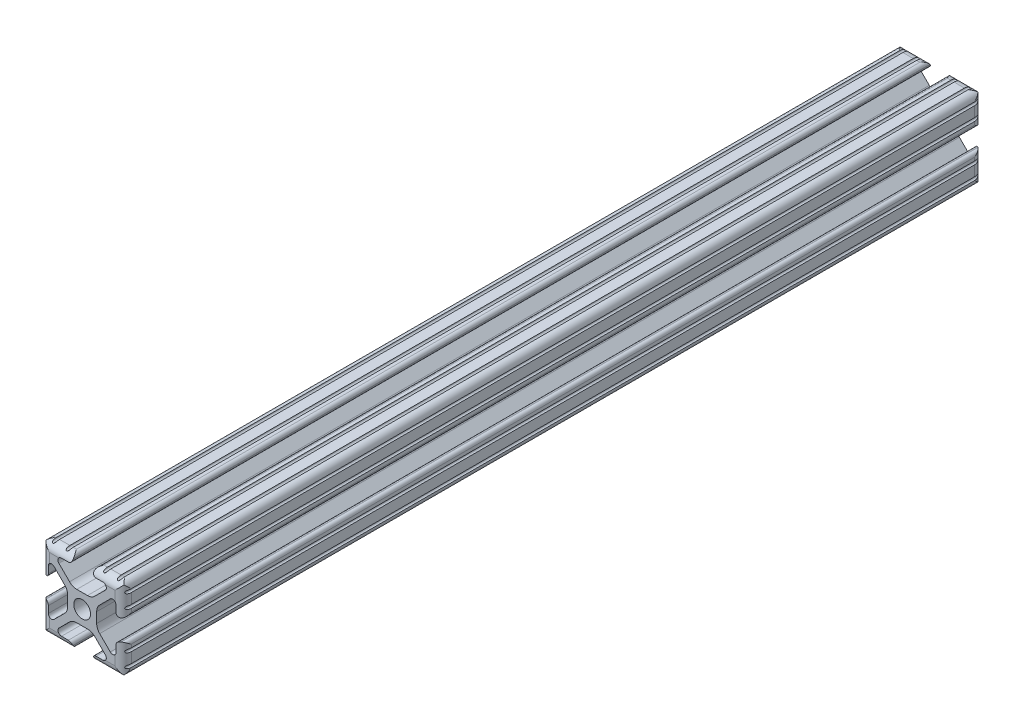
SolidWorks part; units mm, degrees
material "6061 Alloy"
ref_plane "Front Plane" through (0, 0, 0) normal (0, 0, 1) x (1, 0, 0)
ref_plane "Top Plane" through (0, 0, 0) normal (0, 1, 0) x (1, 0, 0)
ref_plane "Right Plane" through (0, 0, 0) normal (1, 0, 0) x (0, 0, -1)
sketch "Sketch1" plane through (0, 0, 0) normal (0, 0, 1) x (1, 0, 0)
  line L88 (-7.1797, -8.6452) -> (-3.9523, -5.4237)
  line L89 (-1.7093, -4.4958) -> (1.7093, -4.4958)
  line L90 (3.9523, -5.4237) -> (7.1797, -8.6452)
  line L91 (6.4164, -10.4902) -> (4.2875, -10.4902)
  line L92 (3.2385, -11.5392) -> (3.2385, -11.651)
  line L93 (4.2875, -12.7) -> (5.3171, -12.7)
  line L94 (6.3331, -12.7) -> (9.5504, -12.7)
  line L95 (12.7, -9.5504) -> (12.7, -6.3331)
  line L96 (12.7, -5.3171) -> (12.7, -4.2875)
  line L97 (11.651, -3.2385) -> (11.5392, -3.2385)
  line L98 (10.4902, -4.2875) -> (10.4902, -6.4021)
  line L99 (8.7371, -7.1294) -> (5.441, -3.8408)
  line L100 (4.5085, -1.5932) -> (4.5085, 1.5932)
  line L101 (5.441, 3.8408) -> (8.7371, 7.1294)
  line L102 (10.4902, 6.4021) -> (10.4902, 4.2875)
  line L103 (11.5392, 3.2385) -> (11.651, 3.2385)
  line L104 (12.7, 4.2875) -> (12.7, 5.3171)
  line L105 (12.7, 6.3331) -> (12.7, 9.5504)
  line L106 (9.5504, 12.7) -> (6.3331, 12.7)
  line L107 (5.3171, 12.7) -> (4.2875, 12.7)
  line L108 (3.2385, 11.651) -> (3.2385, 11.5392)
  line L109 (4.2875, 10.4902) -> (6.4768, 10.4902)
  line L110 (7.207, 8.7244) -> (3.8983, 5.4232)
  line L111 (1.6558, 4.4958) -> (-1.6558, 4.4958)
  line L112 (-3.8983, 5.4232) -> (-7.207, 8.7244)
  line L113 (-6.4768, 10.4902) -> (-4.2875, 10.4902)
  line L114 (-3.2385, 11.5392) -> (-3.2385, 11.651)
  line L115 (-4.2875, 12.7) -> (-5.3171, 12.7)
  line L116 (-6.3331, 12.7) -> (-9.5504, 12.7)
  line L117 (-12.7, 9.5504) -> (-12.7, 6.3331)
  line L118 (-12.7, 5.3171) -> (-12.7, 4.2875)
  line L119 (-11.651, 3.2385) -> (-11.5392, 3.2385)
  line L120 (-10.4902, 4.2875) -> (-10.4902, 6.4021)
  line L121 (-8.7371, 7.1294) -> (-5.441, 3.8408)
  line L122 (-4.5085, 1.5932) -> (-4.5085, -1.5932)
  line L123 (-5.441, -3.8408) -> (-8.7371, -7.1294)
  line L124 (-10.4902, -6.4021) -> (-10.4902, -4.2875)
  line L125 (-11.5392, -3.2385) -> (-11.651, -3.2385)
  line L126 (-12.7, -4.2875) -> (-12.7, -5.3171)
  line L127 (-12.7, -6.3331) -> (-12.7, -9.5504)
  line L128 (-9.5504, -12.7) -> (-6.3331, -12.7)
  line L129 (-5.3171, -12.7) -> (-4.2875, -12.7)
  line L130 (-3.2385, -11.651) -> (-3.2385, -11.5392)
  line L131 (-4.2875, -10.4902) -> (-6.4164, -10.4902)
  circle A1 centre (0, 0) radius 2.6035
  arc A104 (-7.1797, -8.6452) -> (-6.4164, -10.4902) centre (-6.4164, -9.4098) ccw
  arc A105 (-1.7093, -4.4958) -> (-3.9523, -5.4237) centre (-1.7093, -7.6708) ccw
  arc A106 (3.9523, -5.4237) -> (1.7093, -4.4958) centre (1.7093, -7.6708) ccw
  arc A107 (6.4164, -10.4902) -> (7.1797, -8.6452) centre (6.4164, -9.4098) ccw
  arc A108 (4.2875, -10.4902) -> (3.2385, -11.5392) centre (4.2875, -11.5392) ccw
  arc A109 (3.2385, -11.651) -> (4.2875, -12.7) centre (4.2875, -11.651) ccw
  arc A110 (6.3331, -12.7) -> (5.3171, -12.7) centre (5.8251, -12.7) ccw
  arc A111 (10.5664, -12.6998) -> (9.5504, -12.7) centre (10.0584, -12.7) ccw
  arc A112 (10.5664, -12.6998) -> (12.6998, -10.5664) centre (10.5918, -10.5918) ccw
  arc A113 (12.7, -9.5504) -> (12.6998, -10.5664) centre (12.7, -10.0584) ccw
  arc A114 (12.7, -5.3171) -> (12.7, -6.3331) centre (12.7, -5.8251) ccw
  arc A115 (12.7, -4.2875) -> (11.651, -3.2385) centre (11.651, -4.2875) ccw
  arc A116 (11.5392, -3.2385) -> (10.4902, -4.2875) centre (11.5392, -4.2875) ccw
  arc A117 (8.7371, -7.1294) -> (10.4902, -6.4021) centre (9.4628, -6.4021) ccw
  arc A118 (4.5085, -1.5932) -> (5.441, -3.8408) centre (7.6835, -1.5932) ccw
  arc A119 (5.441, 3.8408) -> (4.5085, 1.5932) centre (7.6835, 1.5932) ccw
  arc A120 (10.4902, 6.4021) -> (8.7371, 7.1294) centre (9.4628, 6.4021) ccw
  arc A121 (10.4902, 4.2875) -> (11.5392, 3.2385) centre (11.5392, 4.2875) ccw
  arc A122 (11.651, 3.2385) -> (12.7, 4.2875) centre (11.651, 4.2875) ccw
  arc A123 (12.7, 6.3331) -> (12.7, 5.3171) centre (12.7, 5.8251) ccw
  arc A124 (12.6998, 10.5664) -> (12.7, 9.5504) centre (12.7, 10.0584) ccw
  arc A125 (12.6998, 10.5664) -> (10.5664, 12.6998) centre (10.5918, 10.5918) ccw
  arc A126 (9.5504, 12.7) -> (10.5664, 12.6998) centre (10.0584, 12.7) ccw
  arc A127 (5.3171, 12.7) -> (6.3331, 12.7) centre (5.8251, 12.7) ccw
  arc A128 (4.2875, 12.7) -> (3.2385, 11.651) centre (4.2875, 11.651) ccw
  arc A129 (3.2385, 11.5392) -> (4.2875, 10.4902) centre (4.2875, 11.5392) ccw
  arc A130 (7.207, 8.7244) -> (6.4768, 10.4902) centre (6.4768, 9.4563) ccw
  arc A131 (1.6558, 4.4958) -> (3.8983, 5.4232) centre (1.6558, 7.6708) ccw
  arc A132 (-3.8983, 5.4232) -> (-1.6558, 4.4958) centre (-1.6558, 7.6708) ccw
  arc A133 (-6.4768, 10.4902) -> (-7.207, 8.7244) centre (-6.4768, 9.4563) ccw
  arc A134 (-4.2875, 10.4902) -> (-3.2385, 11.5392) centre (-4.2875, 11.5392) ccw
  arc A135 (-3.2385, 11.651) -> (-4.2875, 12.7) centre (-4.2875, 11.651) ccw
  arc A136 (-6.3331, 12.7) -> (-5.3171, 12.7) centre (-5.8251, 12.7) ccw
  arc A137 (-10.5664, 12.6998) -> (-9.5504, 12.7) centre (-10.0584, 12.7) ccw
  arc A138 (-10.5664, 12.6998) -> (-12.6998, 10.5664) centre (-10.5918, 10.5918) ccw
  arc A139 (-12.7, 9.5504) -> (-12.6998, 10.5664) centre (-12.7, 10.0584) ccw
  arc A140 (-12.7, 5.3171) -> (-12.7, 6.3331) centre (-12.7, 5.8251) ccw
  arc A141 (-12.7, 4.2875) -> (-11.651, 3.2385) centre (-11.651, 4.2875) ccw
  arc A142 (-11.5392, 3.2385) -> (-10.4902, 4.2875) centre (-11.5392, 4.2875) ccw
  arc A143 (-8.7371, 7.1294) -> (-10.4902, 6.4021) centre (-9.4628, 6.4021) ccw
  arc A144 (-4.5085, 1.5932) -> (-5.441, 3.8408) centre (-7.6835, 1.5932) ccw
  arc A145 (-5.441, -3.8408) -> (-4.5085, -1.5932) centre (-7.6835, -1.5932) ccw
  arc A146 (-10.4902, -6.4021) -> (-8.7371, -7.1294) centre (-9.4628, -6.4021) ccw
  arc A147 (-10.4902, -4.2875) -> (-11.5392, -3.2385) centre (-11.5392, -4.2875) ccw
  arc A148 (-11.651, -3.2385) -> (-12.7, -4.2875) centre (-11.651, -4.2875) ccw
  arc A149 (-12.7, -6.3331) -> (-12.7, -5.3171) centre (-12.7, -5.8251) ccw
  arc A150 (-12.6998, -10.5664) -> (-12.7, -9.5504) centre (-12.7, -10.0584) ccw
  arc A151 (-12.6998, -10.5664) -> (-10.5664, -12.6998) centre (-10.5918, -10.5918) ccw
  arc A152 (-9.5504, -12.7) -> (-10.5664, -12.6998) centre (-10.0584, -12.7) ccw
  arc A153 (-5.3171, -12.7) -> (-6.3331, -12.7) centre (-5.8251, -12.7) ccw
  arc A154 (-4.2875, -12.7) -> (-3.2385, -11.651) centre (-4.2875, -11.651) ccw
  arc A155 (-3.2385, -11.5392) -> (-4.2875, -10.4902) centre (-4.2875, -11.5392) ccw
extrude "Boss-Extrude1" add sketch "Sketch1" along normal mid plane 266.7
sketch "Sketch3" plane through (-12.7, 0, 0) normal (-1, 0, 0) x (0, 0, 1)
  line L0 (-133.35, 0) -> (133.35, 0) construction
  line L1 (133.35, -12.6998) -> (-133.35, -12.6998) construction
  line L2 (133.35, -12.6998) -> (133.35, 12.6998) construction
  line L3 (133.35, 12.6998) -> (-133.35, 12.6998) construction
  line L4 (-133.35, -12.6998) -> (-133.35, 12.6998) construction
  circle A0 centre (101.6, 0) radius 3.175
  circle A1 centre (82.55, 0) radius 3.175
  dimension "D1" = 31.75
  dimension "D3" = 6.35
  dimension "D2" = 19.05
fillet "Fillet1" radius 2.54 16 edges at (-12.7, 7.9417, 133.35) (-7.9418, 12.7, 133.35) (7.9418, 12.7, 133.35) (12.7, 7.9417, 133.35) (12.7, -7.9417, 133.35) (7.9418, -12.7, 133.35) (-7.9418, -12.7, 133.35) (-12.7, -7.9417, 133.35) (12.7, 7.9417, -133.35) (12.7, -7.9417, -133.35) (7.9418, -12.7, -133.35) (-7.9418, -12.7, -133.35) (-12.7, -7.9417, -133.35) (-12.7, 7.9417, -133.35) (-7.9418, 12.7, -133.35) (7.9418, 12.7, -133.35)
extrude "Cut-Extrude1" cut sketch "Sketch3" against normal through all
